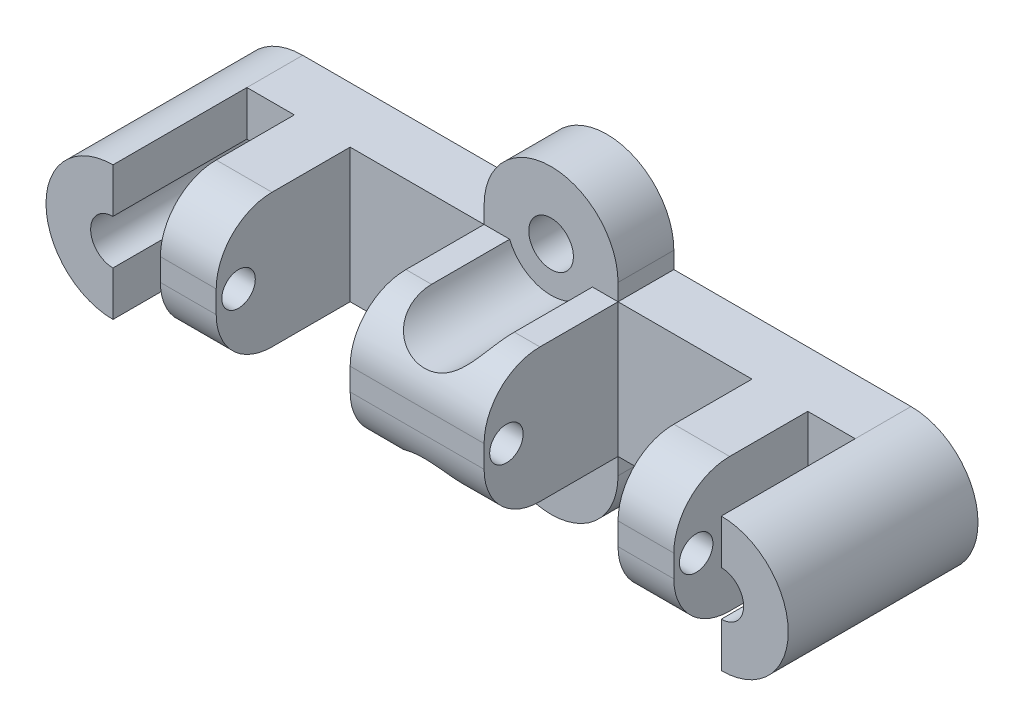
SolidWorks part; units mm, degrees
ref_plane "Front Plane" through (0, 0, 0) normal (0, 0, 1) x (1, 0, 0)
ref_plane "Top Plane" through (0, 0, 0) normal (0, 1, 0) x (1, 0, 0)
ref_plane "Right Plane" through (0, 0, 0) normal (1, 0, 0) x (0, 0, -1)
ref_plane "Plane4" through (0, 0, 8) normal (0, 0, 1) x (1, 0, 0)
sketch "Sketch1" plane through (0, 0, 8) normal (0, 0, 1) x (1, 0, 0)
  line L0 (-6, 57.5) -> (-6, 56)
  line L1 (-6, 56) -> (-27.25, 56)
  line L2 (-27.25, 44) -> (-6, 44)
  line L3 (-6, 44) -> (-6, 42.5)
  line L4 (6, 42.5) -> (6, 44)
  line L5 (6, 44) -> (27.25, 44)
  line L6 (27.25, 56) -> (6, 56)
  line L7 (6, 56) -> (6, 57.5)
  arc A0 (-27.25, 56) -> (-27.25, 44) centre (-27.25, 50) ccw
  arc A1 (-6, 42.5) -> (6, 42.5) centre (0, 42.5) ccw
  arc A2 (27.25, 44) -> (27.25, 56) centre (27.25, 50) ccw
  arc A3 (6, 57.5) -> (-6, 57.5) centre (0, 57.5) ccw
extrude "Boss-Extrude1" add sketch "Sketch1" against normal blind 5
sketch "Sketch2" plane through (0, 0, 8) normal (0, 0, 1) x (1, 0, 0)
  line L0 (27.25, 44) -> (18, 44)
  line L1 (18, 44) -> (18, 56)
  line L2 (18, 56) -> (27.25, 56)
  arc A0 (27.25, 56) -> (27.25, 44) centre (27.25, 50) cw
extrude "Boss-Extrude2" add sketch "Sketch2" along normal blind 12
sketch "Sketch3" plane through (0, 0, 8) normal (0, 0, 1) x (1, 0, 0)
  line L0 (-27.25, 56) -> (-18, 56)
  line L1 (-18, 56) -> (-18, 44)
  line L2 (-18, 44) -> (-27.25, 44)
  arc A0 (-27.25, 44) -> (-27.25, 56) centre (-27.25, 50) cw
extrude "Boss-Extrude3" add sketch "Sketch3" along normal blind 12
sketch "Sketch4" plane through (0, 56, 0) normal (0, 1, 0) x (-1, 0, 0)
  line L0 (-27.25, 8) -> (-23, 8)
  line L1 (-23, 8) -> (-23, 20)
  line L2 (-23, 20) -> (-27.25, 20)
  line L3 (-27.25, 20) -> (-27.25, 8)
extrude "Cut-Extrude1" cut sketch "Sketch4" against normal through all
sketch "Sketch5" plane through (0, 56, 0) normal (0, 1, 0) x (-1, 0, 0)
  line L0 (23, 8) -> (27.25, 8)
  line L1 (27.25, 8) -> (27.25, 20)
  line L2 (27.25, 20) -> (23, 20)
  line L3 (23, 20) -> (23, 8)
extrude "Cut-Extrude2" cut sketch "Sketch5" against normal through all
ref_plane "Plane5" through (0, 0, 20) normal (0, 0, 1) x (1, 0, 0)
sketch "Sketch6" plane through (0, 0, 20) normal (0, 0, 1) x (1, 0, 0)
  line L0 (6, 44) -> (6, 56)
  line L1 (6, 56) -> (3.7081, 56)
  line L2 (-3.7081, 56) -> (-6, 56)
  line L3 (-6, 56) -> (-6, 44)
  line L4 (-6, 44) -> (-3.7081, 44)
  line L5 (3.6202, 44.2011) -> (6, 44)
  arc A0 (3.7081, 56) -> (-3.7081, 56) centre (0, 57.5) cw
  arc A1 (-3.7081, 44) -> (3.6202, 44.2011) centre (0, 42.5) cw
extrude "Boss-Extrude4" add sketch "Sketch6" against normal up to next
hole_wizard "Ø3.0 (3) Diameter Hole1" positions "Sketch8" profile "Sketch7" hole size "Ø3.0" standard "ANSI Metric"
sketch "Sketch8" plane through (-6, 0, 0) normal (-1, 0, 0) x (0, 0, 1)
  point P0 (18, 50)
sketch "Sketch7" plane through (-6, 50, 18) normal (0, 1, 0) x (0, 0, 1)
  line L0 (0, 0) -> (0, 12)
  line L1 (0, 12) -> (1.5, 12)
  line L2 (1.5, 12) -> (1.5, 0)
  line L5 (1.5, 0) -> (0, 0)
  line L11 (0, -6.35) -> (0, 107.95) construction
  dimension "Thru Hole Dia." = 3
  dimension "Thru Hole Depth" = 12
hole_wizard "Ø3.0 (3) Diameter Hole2" positions "Sketch10" profile "Sketch9" hole size "Ø3.0" standard "ANSI Metric"
sketch "Sketch10" plane through (23, 0, 0) normal (1, 0, 0) x (0, 0, -1)
  point P0 (-18, 50)
sketch "Sketch9" plane through (23, 50, 18) normal (0, 1, 0) x (0, 0, -1)
  line L0 (0, 0) -> (0, 5)
  line L1 (0, 5) -> (1.5, 5)
  line L2 (1.5, 5) -> (1.5, 0)
  line L5 (1.5, 0) -> (0, 0)
  line L11 (0, -6.35) -> (0, 107.95) construction
  dimension "Thru Hole Dia." = 3
  dimension "Thru Hole Depth" = 5
hole_wizard "Ø3.0 (3) Diameter Hole3" positions "Sketch12" profile "Sketch11" hole size "Ø3.0" standard "ANSI Metric"
sketch "Sketch12" plane through (-18, 0, 0) normal (1, 0, 0) x (0, 0, -1)
  point P0 (-18, 50)
sketch "Sketch11" plane through (-18, 50, 18) normal (0, 1, 0) x (0, 0, -1)
  line L0 (0, 0) -> (0, 5)
  line L1 (0, 5) -> (1.5, 5)
  line L2 (1.5, 5) -> (1.5, 0)
  line L5 (1.5, 0) -> (0, 0)
  line L11 (0, -6.35) -> (0, 107.95) construction
  dimension "Thru Hole Dia." = 3
  dimension "Thru Hole Depth" = 5
hole_wizard "Ø4.0 (4) Diameter Hole1" positions "Sketch14" profile "Sketch13" hole size "Ø4.0" standard "ANSI Metric"
sketch "Sketch14" plane through (0, 0, 3) normal (0, 0, -1) x (-1, 0, 0)
  point P0 (0, 57.5)
  point P1 (-27.25, 50)
  point P2 (27.25, 50)
  point P3 (0, 42.5)
sketch "Sketch13" plane through (0, 57.5, 3) normal (1, 0, 0) x (0, 1, 0)
  line L0 (0, 0) -> (0, 17)
  line L1 (0, 17) -> (2, 17)
  line L2 (2, 17) -> (2, 0)
  line L5 (2, 0) -> (0, 0)
  line L11 (0, -6.35) -> (0, 107.95) construction
  dimension "Thru Hole Dia." = 4
  dimension "Thru Hole Depth" = 17
fillet "Fillet1" radius 5 6 edges at (-20.5, 56, 20) (20.5, 44, 20) (20.5, 56, 20) (-4.854, 44, 20) (4.854, 56, 20) (-20.5, 44, 20) tangent propagation no
sketch "Sketch15" plane through (0, 0, 3) normal (0, 0, -1) x (-1, 0, 0)
  line L1 (52.4419, 17.1639) -> (-50.3694, 17.1639)
  line L2 (52.4419, 17.1639) -> (52.4419, 95.8111)
  line L3 (52.4419, 95.8111) -> (-50.3694, 95.8111)
  line L4 (-50.3694, 17.1639) -> (-50.3694, 95.8111)
  point P4 (-50.3694, 95.8111)
extrude "Cut-Extrude3" cut sketch "Sketch15" along normal blind 10 rebuild error yes
